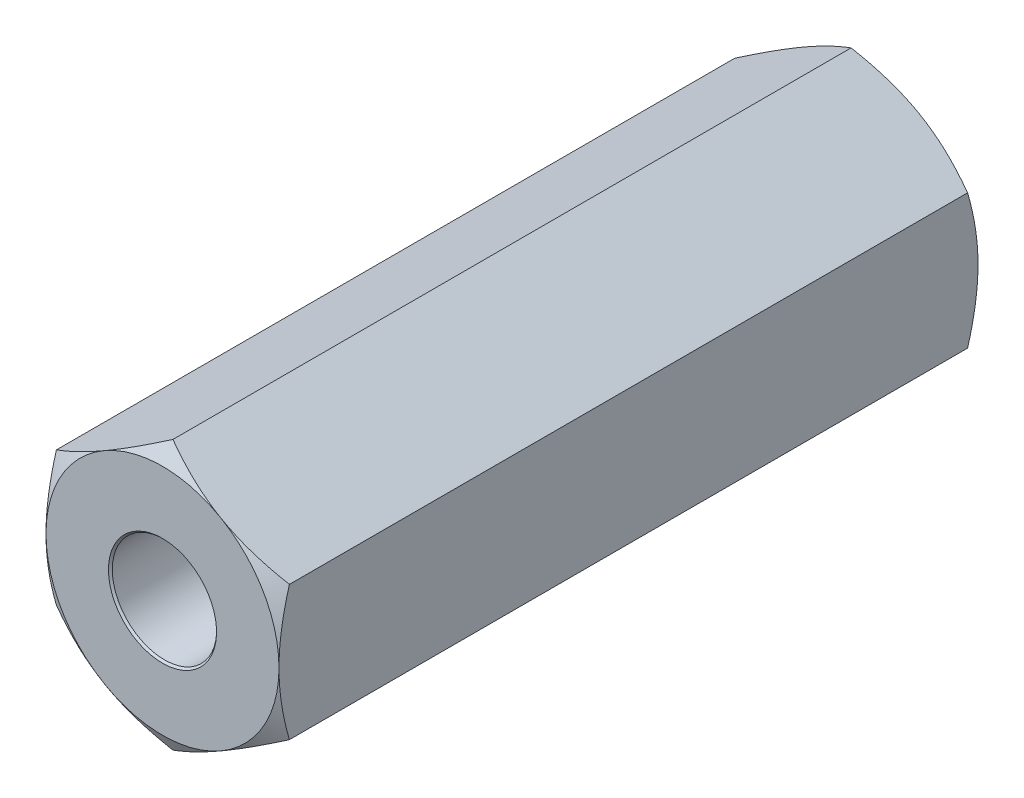
SolidWorks part; units mm, degrees
ref_plane "Front Plane" through (0, 0, 0) normal (0, 0, 1) x (1, 0, 0)
ref_plane "Top Plane" through (0, 0, 0) normal (0, 1, 0) x (1, 0, 0)
ref_plane "Right Plane" through (0, 0, 0) normal (1, 0, 0) x (0, 0, -1)
sketch "Sketch3" plane through (0, 0, 0) normal (1, 0, 0) x (0, 0, -1)
  line L0 (-9.525, 0) -> (9.525, 0) construction
  line L1 (0, 3.175) -> (0, -3.175) construction
  line L2 (-9.525, 1.4224) -> (-9.525, -1.4224) construction
  point P2 (4.7625, 0)
  point P3 (-4.7625, 0)
  dimension "D1" = 4.7625
  dimension "Length" = 19.05
  dimension "Min Thread Length" = 4.7625
  dimension "Thread Dia" = 2.8448
  dimension "Hex" = 6.35
sketch "Sketch1" plane through (0, 0, 0) normal (0, 0, 1) x (1, 0, 0)
  line L1 (0, 3.6662) -> (-3.175, 1.8331)
  line L2 (-3.175, 1.8331) -> (-3.175, -1.8331)
  line L3 (-3.175, -1.8331) -> (0, -3.6662)
  line L4 (0, -3.6662) -> (3.175, -1.8331)
  line L5 (3.175, -1.8331) -> (3.175, 1.8331)
  line L6 (3.175, 1.8331) -> (0, 3.6662)
  circle A0 centre (0, 0) radius 3.175 construction
  circle A1 centre (0, 0) radius 1.4224
extrude "Extrude1" add sketch "Sketch1" along normal up to vertex (9.525 mm away) and the other way up to vertex (9.525 mm away) up to point (0, 0, 9.525) other way up to point (0, 0, -9.525)
sketch "Sketch11" plane through (0, 0, -9.525) normal (0, 0, -1) x (-1, 0, 0)
  circle A0 centre (0, 0) radius 1.4224 construction
  circle A1 centre (0, 0) radius 1.4224
curve "Helix/Spiral1" pitch 0.635 height 19.685 turns 31 parameters "Pitch"=0.635
sketch "Sketch12" plane through (0, 0, 0) normal (1, 0, 0) x (0, 0, -1)
  line L0 (10.0806, 1.4224) -> (9.525, 1.4224)
  line L1 (10.0806, 1.4224) -> (9.8425, 1.01)
  line L2 (9.8425, 1.01) -> (9.7631, 1.01)
  line L3 (9.7631, 1.01) -> (9.525, 1.4224)
  line L4 (9.8028, 1.01) -> (9.8028, 1.4224) construction
  line L5 (9.9616, 1.2162) -> (9.6441, 1.2162) construction
  dimension "D1" = 0.0794
  dimension "D2" = 0.3175
  dimension "D3" = 60
sweep "Sweep1" [suppressed] add profiles "Sketch12" path "Helix/Spiral1"
sketch "Sketch6" plane through (0, 0, -9.525) normal (0, 0, -1) x (-1, 0, 0)
  line L6 (0, 3.6662) -> (-3.175, 1.8331)
  line L7 (-3.175, 1.8331) -> (-3.175, -1.8331)
  line L8 (-3.175, -1.8331) -> (0, -3.6662)
  line L9 (0, -3.6662) -> (3.175, -1.8331)
  line L10 (3.175, -1.8331) -> (3.175, 1.8331)
  line L11 (3.175, 1.8331) -> (0, 3.6662)
  line L12 (0, 3.6662) -> (-3.175, 1.8331)
  line L13 (-3.175, 1.8331) -> (-3.175, -1.8331)
  line L14 (-3.175, -1.8331) -> (0, -3.6662)
  line L15 (0, -3.6662) -> (3.175, -1.8331)
  line L16 (3.175, -1.8331) -> (3.175, 1.8331)
  line L17 (3.175, 1.8331) -> (0, 3.6662)
  dimension "D1" = 0
extrude "Extrude2" [suppressed] cut sketch "Sketch6" along normal through all
sketch "Sketch7" plane through (0, 0, -9.525) normal (0, 0, -1) x (-1, 0, 0)
  circle A2 centre (0, 0) radius 1.4732
  circle A3 centre (0, 0) radius 1.4732
  dimension "D1" = 0.0508
extrude "Extrude3" cut sketch "Sketch7" against normal through all draft 43
sketch "Sketch8" plane through (0, 0, -9.525) normal (0, 0, -1) x (-1, 0, 0)
  circle A0 centre (0, 0) radius 3.175 construction
  circle A1 centre (0, 0) radius 3.175
extrude "Extrude4" cut sketch "Sketch8" against normal through all draft 60 flip side to cut
mirror "Mirror1" about plane through (0, 0, 0) normal (0, 0, 1) of "Extrude2", "Extrude3", "Extrude4"
sketch "Sketch9" [suppressed] plane through (0, 0, 0) normal (1, 0, 0) x (0, 0, -1)
  line L1 (-1.5875, 0.8128) -> (1.5875, 0.8128)
  line L2 (-1.5875, 0.8128) -> (-1.5875, 0)
  line L3 (-1.5875, 0) -> (1.5875, 0)
  line L4 (1.5875, 0.8128) -> (1.5875, 0)
  line L7 (-6.35, 0) -> (6.35, 0) construction
revolve "Revolve" [suppressed] add sketch "Sketch9" angle 360 about L0
sketch "Sketch10" [suppressed] plane through (0, 0, 0) normal (1, 0, 0) x (0, 0, -1)
  line L0 (6.35, 0.762) -> (1.5875, 0.762)
  line L1 (-6.35, 0.762) -> (-1.5875, 0.762)
  line L2 (1.5875, 0.762) -> (1.5875, -0.762)
  line L3 (-6.35, -0.8128) -> (-1.5875, -0.8128)
  line L4 (-1.5875, 0.762) -> (-1.5875, -0.8128)
  line L5 (1.5875, -0.762) -> (6.35, -0.762)
equation "\"D1@Sketch3\" = \"Min Thread Length@Sketch3\""
equation "\"D3@Helix/Spiral1\" = \"Length@Sketch3\"+\"Pitch@Helix/Spiral1\""
equation "\"D1@Sketch12\" = \"Pitch@Helix/Spiral1\"*.125"
equation "\"D2@Sketch12\" = \"Pitch@Helix/Spiral1\"*.5"
